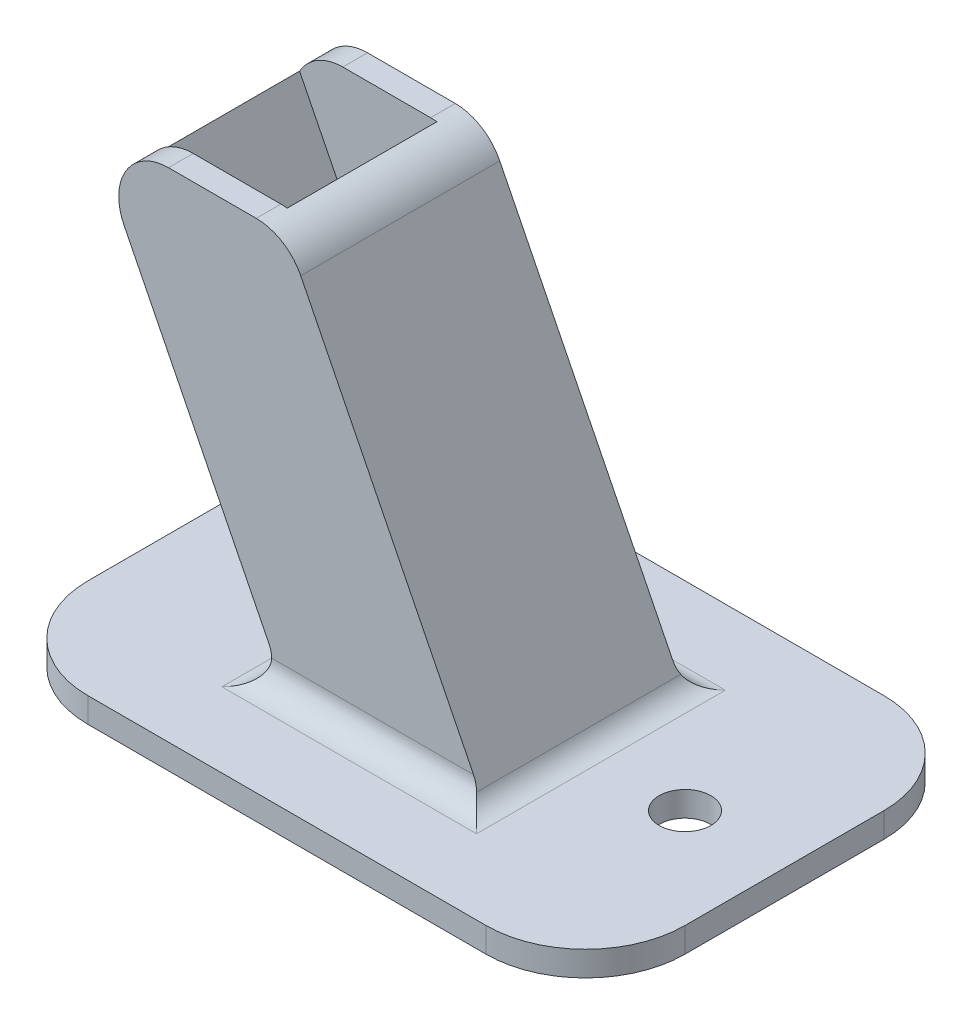
SolidWorks part; units mm, degrees
material "ABS"
ref_plane "Front Plane" through (0, 0, 0) normal (0, 0, 1) x (1, 0, 0)
ref_plane "Top Plane" through (0, 0, 0) normal (0, 1, 0) x (1, 0, 0)
ref_plane "Right Plane" through (0, 0, 0) normal (1, 0, 0) x (0, 0, -1)
sketch "Sketch1" plane through (0, 0, 0) normal (0, 1, 0) x (1, 0, 0)
  line L1 (-7.4428, 19.2272) -> (17.9572, 19.2272)
  line L2 (-13.7928, 12.8772) -> (-13.7928, 0.1772)
  line L3 (-7.4428, -6.1728) -> (17.9572, -6.1728)
  line L4 (24.3072, 12.8772) -> (24.3072, 0.1772)
  arc A0 (24.3072, 12.8772) -> (17.9572, 19.2272) centre (17.9572, 12.8772) ccw
  arc A1 (24.3072, 0.1772) -> (17.9572, -6.1728) centre (17.9572, 0.1772) cw
  arc A2 (-7.4428, -6.1728) -> (-13.7928, 0.1772) centre (-7.4428, 0.1772) cw
  arc A3 (-7.4428, 19.2272) -> (-13.7928, 12.8772) centre (-7.4428, 12.8772) ccw
  point P8 (24.3072, -6.1728)
  point P11 (-13.7928, -6.1728)
  dimension "D3" = 6.35
  dimension "D1" = 25.4
  dimension "D2" = 38.1
extrude "Boss-Extrude1" add sketch "Sketch1" along normal blind 1.5875
sketch "Sketch2" plane through (0, 1.5875, 0) normal (0, 1, 0) x (1, 0, 0)
  line L0 (17.9572, 19.2272) -> (-7.4428, 19.2272) construction
  line L1 (-1.0928, 12.8772) -> (11.6072, 12.8772)
  line L2 (-1.0928, 12.8772) -> (-1.0928, 0.1772)
  line L3 (-1.0928, 0.1772) -> (11.6072, 0.1772)
  line L4 (11.6072, 12.8772) -> (11.6072, 0.1772)
  line L5 (-13.7928, 12.8772) -> (-13.7928, 0.1772) construction
  line L6 (5.2572, 19.2272) -> (5.2572, 12.8772) construction
  line L7 (5.2572, 0.1772) -> (5.2572, -6.1728) construction
  line L8 (-7.4428, -6.1728) -> (17.9572, -6.1728) construction
  line L9 (0.482, 11.3024) -> (0.482, 1.752)
  line L10 (0.482, 1.752) -> (10.0324, 1.752)
  line L11 (10.0324, 11.3024) -> (10.0324, 1.752)
  line L12 (0.482, 11.3024) -> (10.0324, 11.3024)
  point P4 (5.2572, 12.8772)
  point P5 (-1.0928, 6.5272)
  point P6 (5.2572, 19.2272)
  point P7 (-13.7928, 6.5272)
  dimension "D1" = 12.7
  dimension "D2" = 12.7
  dimension "D3" = 1.5748
ref_plane "Plane1" through (0, 26.9875, 0) normal (0, 1, 0) x (1, 0, 0)
sketch "Sketch3" plane through (0, 26.9875, 0) normal (0, 1, 0) x (1, 0, 0)
  line L0 (-1.0928, 12.8772) -> (-1.0928, 0.1772) construction
  line L1 (-1.0928, 12.8772) -> (11.6072, 12.8772) construction
  line L2 (-1.0928, 0.1772) -> (11.6072, 0.1772) construction
  line L3 (11.6072, 12.8772) -> (11.6072, 0.1772) construction
  line L4 (-1.0928, 12.8772) -> (-1.0928, 0.1772) construction
  line L5 (-1.0928, 12.8772) -> (11.6072, 12.8772) construction
  line L6 (-1.0928, 0.1772) -> (11.6072, 0.1772) construction
  line L7 (11.6072, 12.8772) -> (11.6072, 0.1772) construction
  line L8 (-13.7928, 12.8772) -> (-13.7928, 0.1772) construction
  line L9 (-13.7928, 12.8772) -> (-1.0928, 12.8772)
  line L10 (-13.7928, 12.8772) -> (-13.7928, 0.1772)
  line L11 (-13.7928, 0.1772) -> (-1.0928, 0.1772)
  line L12 (-1.0928, 12.8772) -> (-1.0928, 0.1772)
  line L13 (-12.218, 11.3024) -> (-12.218, 1.752)
  line L14 (-12.218, 1.752) -> (-2.6676, 1.752)
  line L15 (-2.6676, 11.3024) -> (-2.6676, 1.752)
  line L16 (-12.218, 11.3024) -> (-2.6676, 11.3024)
  point P8 (-1.0928, 6.5272)
  point P11 (-13.7928, 6.5272)
  dimension "D1" = 1.5748
loft "Loft3" add section "Sketch2" section "Sketch3" connector at (11.6072, 1.5875, -12.8772) connector at (-1.0928, 26.9875, -12.8772)
loft "Cut-Loft1" cut section "Sketch3<243>" section "Sketch2<111>" connector at (-2.6676, 26.9875, -11.3024) connector at (10.0324, 1.5875, -11.3024)
sketch "Sketch3<243>" plane through (0, 26.9875, 0) normal (0, 1, 0) x (1, 0, 0) same geometry as "Sketch3"
sketch "Sketch2<111>" plane through (0, 1.5875, 0) normal (0, 1, 0) x (1, 0, 0) same geometry as "Sketch2"
fillet "Fillet1" radius 3.175 1 edges
fillet "Fillet2" radius 3.175 1 edges
fillet "Fillet3" radius 1.5875 4 edges
ref_plane "Plane2" through (0, 0, -6.5272) normal (0, 0, -1) x (-1, 0, 0)
sketch "Sketch4" plane through (0, 0, 0) normal (0, -1, 0) x (-1, 0, 0)
  line L0 (7.4428, -6.1728) -> (7.4428, 19.2272) construction
  line L1 (-17.9572, -6.1728) -> (-17.9572, 19.2272) construction
  line L2 (7.4428, -6.1728) -> (-17.9572, -6.1728) construction
  arc A0 (-24.3072, 0.1772) -> (-17.9572, -6.1728) centre (-17.9572, 0.1772) ccw construction
  circle A1 centre (7.4428, 6.5272) radius 1.651
  circle A2 centre (-17.9572, 6.5272) radius 1.651
  dimension "D1" = 3.302
extrude "Cut-Extrude2" cut sketch "Sketch4" against normal up to next
